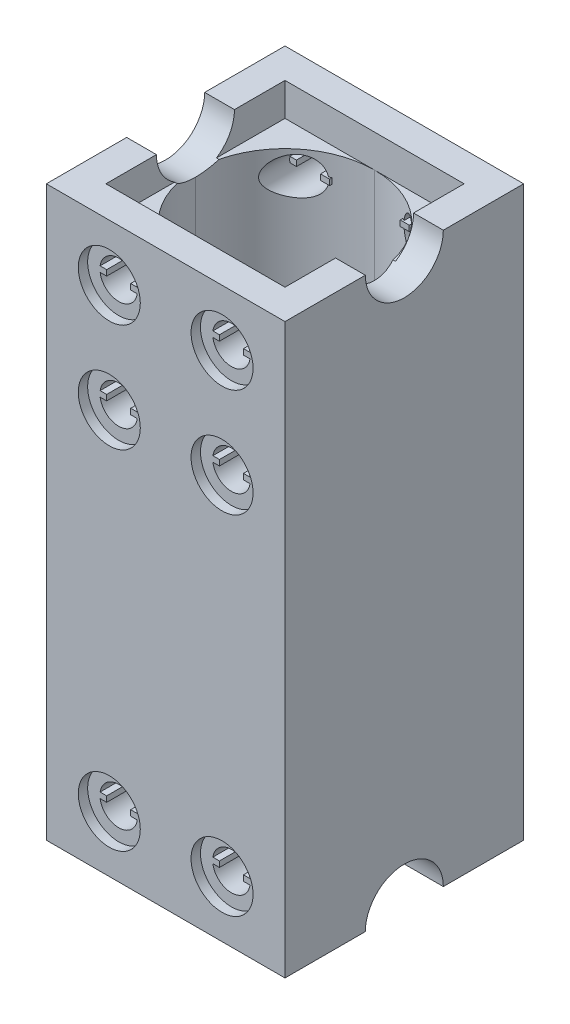
SolidWorks part; units mm, degrees
ref_plane "Front Plane" through (0, 0, 0) normal (0, 0, 1) x (1, 0, 0)
ref_plane "Top Plane" through (0, 0, 0) normal (0, 1, 0) x (1, 0, 0)
ref_plane "Right Plane" through (0, 0, 0) normal (1, 0, 0) x (0, 0, -1)
sketch "Sketch1" plane through (0, 0, 0) normal (0, 1, 0) x (1, 0, 0)
  line L0 (0, 0) -> (0, 21.2255) construction
  line L1 (0, 0) -> (25.5176, 0) construction
  line L2 (-9.525, 9.525) -> (-9.525, -9.525)
  line L3 (-12.7, 12.7) -> (12.7, 12.7)
  line L4 (-12.7, 12.7) -> (-12.7, -12.7)
  line L5 (-12.7, -12.7) -> (12.7, -12.7)
  line L6 (12.7, 12.7) -> (12.7, -12.7)
  line L7 (-9.525, -9.525) -> (9.525, -9.525)
  line L8 (9.525, 9.525) -> (9.525, -9.525)
  line L9 (-9.525, 9.525) -> (9.525, 9.525)
  dimension "D1" = 25.4
  dimension "D2" = 25.4
  dimension "D3" = 3.175
extrude "Boss-Extrude1" add sketch "Sketch1" along normal mid plane 60.5
sketch "Sketch2" plane through (0, 0, 12.7) normal (0, 0, -1) x (-1, 0, 0)
  line L0 (0, 0) -> (0, 30.8399) construction
  line L2 (-12.7, 30.25) -> (12.7, 30.25) construction
  circle A0 centre (-6, 24.25) radius 2
  circle A1 centre (6, 24.25) radius 2
  dimension "D1" = 4
  dimension "D2" = 6
  dimension "D3" = 12
extrude "Cut-Extrude1" cut sketch "Sketch2" along normal through all
ref_axis "Axis1" through (0, 32.3819, 0) along (0, -1, 0)
sketch "Sketch3" plane through (12.7, 0, 0) normal (1, 0, 0) x (0, 0, -1)
  line L0 (-12.7, -30.25) -> (12.7, -30.25) construction
  line L1 (-4.15, -30.25) -> (4.15, -30.25)
  arc A0 (4.15, -30.25) -> (-4.15, -30.25) centre (0, -30.25) ccw
  dimension "D1" = 8.3
extrude "Cut-Extrude2" cut sketch "Sketch3" against normal through all
mirror "Mirror2" about plane through (0, 0, 0) normal (0, 1, 0) of "Cut-Extrude2", "Cut-Extrude1"
sketch "Sketch9" plane through (0, 0, 12.7) normal (0, 0, 1) x (1, 0, 0)
  line L0 (-6, 24.25) -> (-6, 3.1588) construction
  line L1 (6, 24.25) -> (6, 3.1588) construction
  circle A0 centre (-6, 12.75) radius 2
  circle A1 centre (6, 12.75) radius 2
  circle A2 centre (-6, 24.25) radius 2 construction
  dimension "D1" = 11.5
extrude "Cut-Extrude7" cut sketch "Sketch9" against normal up to next
fillet "Fillet1" radius 9.5 4 edges at (-9.525, 0, -9.525) (-9.525, 0, 9.525) (9.525, 0, 9.525) (9.525, 0, -9.525)
sketch "Sketch4" plane through (0, -30.25, 0) normal (0, 1, 0) x (1, 0, 0)
  line L0 (0, 0) -> (0, 13.3868) construction
  line L1 (0, 0) -> (17.4828, 0) construction
  circle A0 centre (7.78, -7.78) radius 1.175
  circle A1 centre (-7.78, -7.78) radius 1.175
  circle A2 centre (7.78, 7.78) radius 1.175
  circle A3 centre (-7.78, 7.78) radius 1.175
  dimension "D3" = 2.35
  dimension "D1" = 15.56
  dimension "D2" = 15.56
sketch "Sketch7" plane through (0, 30.25, 0) normal (0, 1, 0) x (1, 0, 0)
  line L0 (0, 0) -> (0, 13.6655) construction
  line L1 (0, 0) -> (18.6104, 0) construction
  line L3 (-9.53, 9.53) -> (9.53, 9.53)
  line L4 (-9.53, 9.53) -> (-9.53, -9.53)
  line L5 (-9.53, -9.53) -> (9.53, -9.53)
  line L6 (9.53, 9.53) -> (9.53, -9.53)
  dimension "D1" = 19.06
extrude "Cut-Extrude4" cut sketch "Sketch7" against normal blind 3.5
extrude "Cut-Extrude5" cut sketch "Sketch4" along normal blind 2.4
sketch "Sketch10" plane through (0, -30.25, 0) normal (0, -1, 0) x (1, 0, 0)
  circle A0 centre (-7.78, 7.78) radius 2.15 construction
  circle A1 centre (-7.78, 7.78) radius 3.75 construction
  dimension "D1" = 4.3
  dimension "D2" = 7.5
sketch "Sketch11" plane through (0, -30.25, 0) normal (0, -1, 0) x (1, 0, 0)
  line L0 (0, 0) -> (0, 13.4046) construction
  line L5 (0, 13.4046) -> (-0.0317, 13.4363) construction
  line L6 (0, 0) -> (16.0538, 0) construction
  line L7 (-7.78, 10.6668) -> (-10.28, 9.2234) construction
  line L8 (-10.28, 9.2234) -> (-10.28, 6.3366) construction
  line L9 (-10.28, 6.3366) -> (-7.78, 4.8932) construction
  line L10 (-7.78, 4.8932) -> (-5.28, 6.3366) construction
  line L11 (-5.28, 6.3366) -> (-5.28, 9.2234) construction
  line L12 (-5.28, 9.2234) -> (-7.78, 10.6668) construction
  line L13 (-5.18, 6.2789) -> (-5.18, 9.2811)
  line L14 (-5.18, 9.2811) -> (-7.78, 10.7822)
  line L15 (-7.78, 10.7822) -> (-10.38, 9.2811)
  line L16 (-10.38, 9.2811) -> (-10.38, 6.2789)
  line L17 (-10.38, 6.2789) -> (-7.78, 4.7778)
  line L18 (-7.78, 4.7778) -> (-5.18, 6.2789)
  line L19 (10.38, 6.2789) -> (7.78, 4.7778)
  line L20 (10.38, 9.2811) -> (10.38, 6.2789)
  line L21 (7.78, 10.7822) -> (10.38, 9.2811)
  line L22 (5.18, 9.2811) -> (7.78, 10.7822)
  line L23 (5.18, 6.2789) -> (5.18, 9.2811)
  line L24 (7.78, 4.7778) -> (5.18, 6.2789)
  line L25 (5.18, -9.2811) -> (7.78, -10.7822)
  line L26 (7.78, -10.7822) -> (10.38, -9.2811)
  line L27 (10.38, -9.2811) -> (10.38, -6.2789)
  line L28 (10.38, -6.2789) -> (7.78, -4.7778)
  line L29 (7.78, -4.7778) -> (5.18, -6.2789)
  line L30 (5.18, -6.2789) -> (5.18, -9.2811)
  line L31 (-10.38, -6.2789) -> (-7.78, -4.7778)
  line L32 (-10.38, -9.2811) -> (-10.38, -6.2789)
  line L33 (-7.78, -10.7822) -> (-10.38, -9.2811)
  line L34 (-5.18, -9.2811) -> (-7.78, -10.7822)
  line L35 (-5.18, -6.2789) -> (-5.18, -9.2811)
  line L36 (-7.78, -4.7778) -> (-5.18, -6.2789)
  circle A1 centre (-7.78, 7.78) radius 2.5 construction
  dimension "D2" = 5
  dimension "D3" = 120
  dimension "D4" = 120
  dimension "D5" = 120
  dimension "D6" = 120
  dimension "D7" = 0.1
extrude "Cut-Extrude8" cut sketch "Sketch11" against normal blind 2.4
ref_plane "Plane1" through (0, 0, 11.9) normal (0, 0, 1) x (1, 0, 0)
sketch "Sketch13" plane through (0, 0, 11.9) normal (0, 0, 1) x (1, 0, 0)
  line L0 (-6, 24.25) -> (-11.1534, 24.25) construction
  line L1 (-7.9774, 24.55) -> (-8.2444, 24.55)
  line L2 (-7.9774, 24.55) -> (-7.2774, 24.55)
  line L3 (-8.2444, 24.55) -> (-8.2444, 23.95)
  line L4 (-7.9774, 23.95) -> (-7.2774, 23.95)
  line L5 (-7.2774, 24.55) -> (-7.2774, 23.95)
  line L6 (-8.2444, 23.95) -> (-7.9774, 23.95)
  line L7 (-6, 24.25) -> (-6, 27.339) construction
  line L8 (0, 0) -> (0, 44.7414) construction
  line L9 (0, 0) -> (-23.4735, 0) construction
  line L10 (-4.0226, 24.55) -> (-3.7556, 24.55)
  line L11 (-4.7226, 24.55) -> (-4.7226, 23.95)
  line L12 (-4.0226, 24.55) -> (-4.7226, 24.55)
  line L13 (-3.7556, 24.55) -> (-3.7556, 23.95)
  line L14 (-3.7556, 23.95) -> (-4.0226, 23.95)
  line L15 (-4.0226, 23.95) -> (-4.7226, 23.95)
  line L16 (7.2774, 24.55) -> (7.2774, 23.95)
  line L17 (7.9774, 24.55) -> (7.2774, 24.55)
  line L18 (7.9774, 24.55) -> (8.2444, 24.55)
  line L19 (8.2444, 24.55) -> (8.2444, 23.95)
  line L20 (8.2444, 23.95) -> (7.9774, 23.95)
  line L21 (7.9774, 23.95) -> (7.2774, 23.95)
  line L22 (3.7556, 24.55) -> (3.7556, 23.95)
  line L23 (4.0226, 24.55) -> (3.7556, 24.55)
  line L24 (4.0226, 24.55) -> (4.7226, 24.55)
  line L25 (4.7226, 24.55) -> (4.7226, 23.95)
  line L26 (4.0226, 23.95) -> (4.7226, 23.95)
  line L27 (3.7556, 23.95) -> (4.0226, 23.95)
  line L28 (3.7556, -23.95) -> (4.0226, -23.95)
  line L29 (4.0226, -23.95) -> (4.7226, -23.95)
  line L30 (4.7226, -24.55) -> (4.7226, -23.95)
  line L31 (4.0226, -24.55) -> (4.7226, -24.55)
  line L32 (4.0226, -24.55) -> (3.7556, -24.55)
  line L33 (3.7556, -24.55) -> (3.7556, -23.95)
  line L34 (7.9774, -23.95) -> (7.2774, -23.95)
  line L35 (8.2444, -23.95) -> (7.9774, -23.95)
  line L36 (8.2444, -24.55) -> (8.2444, -23.95)
  line L37 (7.9774, -24.55) -> (8.2444, -24.55)
  line L38 (7.9774, -24.55) -> (7.2774, -24.55)
  line L39 (7.2774, -24.55) -> (7.2774, -23.95)
  line L40 (-4.0226, -23.95) -> (-4.7226, -23.95)
  line L41 (-3.7556, -23.95) -> (-4.0226, -23.95)
  line L42 (-3.7556, -24.55) -> (-3.7556, -23.95)
  line L43 (-4.0226, -24.55) -> (-4.7226, -24.55)
  line L44 (-4.7226, -24.55) -> (-4.7226, -23.95)
  line L45 (-4.0226, -24.55) -> (-3.7556, -24.55)
  line L46 (-8.2444, -23.95) -> (-7.9774, -23.95)
  line L47 (-7.2774, -24.55) -> (-7.2774, -23.95)
  line L48 (-7.9774, -23.95) -> (-7.2774, -23.95)
  line L49 (-8.2444, -24.55) -> (-8.2444, -23.95)
  line L50 (-7.9774, -24.55) -> (-7.2774, -24.55)
  line L51 (-7.9774, -24.55) -> (-8.2444, -24.55)
  circle A1 centre (-6, 24.25) radius 2 construction
  dimension "D1" = 0.6
  dimension "D2" = 0.7
extrude "Boss-Extrude3" add sketch "Sketch13" against normal blind 3.4
mirror "Mirror3" about plane through (0, 0, 0) normal (0, 0, 1) of "Boss-Extrude3"
sketch "Sketch14" plane through (0, 0, 11.9) normal (0, 0, 1) x (1, 0, 0)
  line L0 (-6, 12.75) -> (-9.4415, 12.75) construction
  line L1 (-7.2774, 23.95) -> (-7.2774, 24.55) construction
  line L2 (-7.9774, 13.05) -> (-7.2774, 13.05)
  line L3 (-7.9774, 23.95) -> (-7.2774, 23.95) construction
  line L4 (-7.9774, 12.45) -> (-7.2774, 12.45)
  line L5 (-7.2774, 13.05) -> (-7.2774, 12.45)
  line L6 (-7.9774, 13.05) -> (-8.2151, 13.05)
  line L7 (-8.2151, 13.05) -> (-8.2151, 12.45)
  line L8 (-8.2151, 12.45) -> (-7.9774, 12.45)
  line L9 (-6, 12.75) -> (-6, 15.5669) construction
  line L10 (-4.7226, 13.05) -> (-4.7226, 12.45)
  line L11 (-4.0226, 13.05) -> (-4.7226, 13.05)
  line L12 (-4.0226, 13.05) -> (-3.7849, 13.05)
  line L13 (-3.7849, 13.05) -> (-3.7849, 12.45)
  line L14 (-3.7849, 12.45) -> (-4.0226, 12.45)
  line L15 (-4.0226, 12.45) -> (-4.7226, 12.45)
  line L16 (0, 0) -> (0, 31.8903) construction
  line L17 (4.0226, 12.45) -> (4.7226, 12.45)
  line L18 (3.7849, 12.45) -> (4.0226, 12.45)
  line L19 (3.7849, 13.05) -> (3.7849, 12.45)
  line L20 (4.0226, 13.05) -> (3.7849, 13.05)
  line L21 (4.0226, 13.05) -> (4.7226, 13.05)
  line L22 (4.7226, 13.05) -> (4.7226, 12.45)
  line L23 (8.2151, 12.45) -> (7.9774, 12.45)
  line L24 (8.2151, 13.05) -> (8.2151, 12.45)
  line L25 (7.9774, 13.05) -> (8.2151, 13.05)
  line L26 (7.2774, 13.05) -> (7.2774, 12.45)
  line L27 (7.9774, 12.45) -> (7.2774, 12.45)
  line L28 (7.9774, 13.05) -> (7.2774, 13.05)
  circle A0 centre (-6, 12.75) radius 2 construction
extrude "Boss-Extrude4" add sketch "Sketch14" against normal blind 3.4
sketch "Sketch15" plane through (0, 0, 12.7) normal (0, 0, 1) x (1, 0, 0)
  circle A0 centre (6, 25.8375) radius 1.35 construction
  circle A1 centre (6, 24.25) radius 2 construction
  dimension "D1" = 2.7
  dimension "D2" = 1.5875
sketch "Sketch16" plane through (0, 0, 12.7) normal (0, 0, 1) x (1, 0, 0)
  circle A0 centre (-6, 24.25) radius 3.3
  circle A1 centre (6, 24.25) radius 3.3
  circle A2 centre (-6, -24.25) radius 3.3
  circle A3 centre (6, -24.25) radius 3.3
  dimension "D1" = 6.6
extrude "Cut-Extrude9" cut sketch "Sketch16" against normal blind 1
mirror "Mirror4" about plane through (0, 0, 0) normal (0, 0, 1) of "Cut-Extrude9"
sketch "Sketch17" plane through (0, 0, 12.7) normal (0, 0, 1) x (1, 0, 0)
  circle A0 centre (-6, 12.75) radius 3.3
  circle A1 centre (6, 12.75) radius 3.3
  circle A2 centre (-6, 24.25) radius 3.3 construction
extrude "Cut-Extrude10" cut sketch "Sketch17" against normal up to surface (1 mm away) up to face at (-6, 24.25, 11.7)
